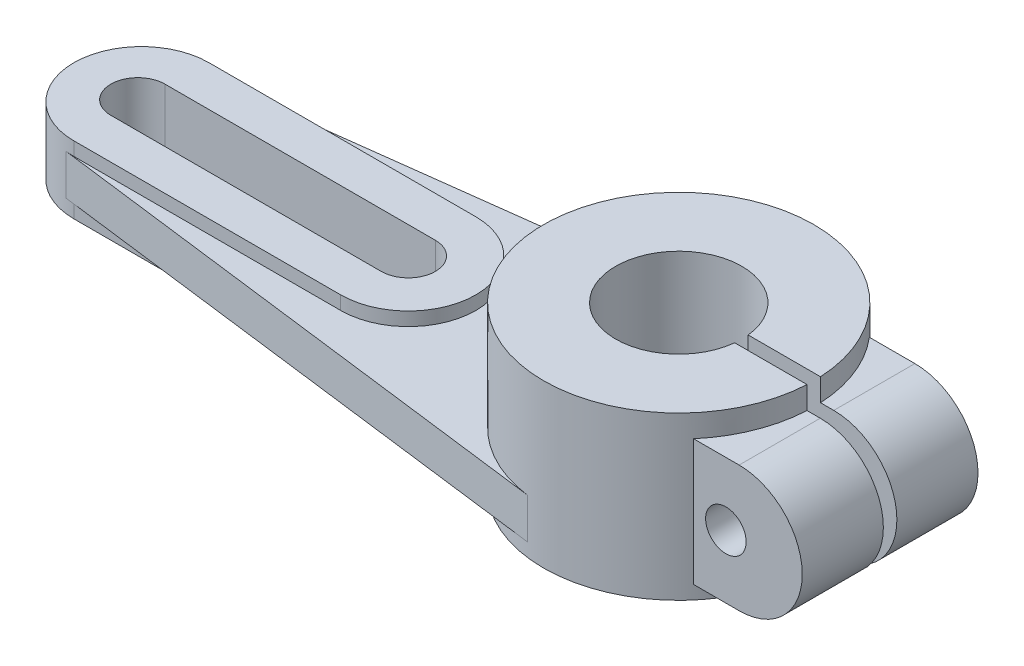
SolidWorks part; units mm, degrees
ref_plane "Front Plane" through (0, 0, 0) normal (0, 0, 1) x (1, 0, 0)
ref_plane "Top Plane" through (0, 0, 0) normal (0, 1, 0) x (1, 0, 0)
ref_plane "Right Plane" through (0, 0, 0) normal (1, 0, 0) x (0, 0, -1)
sketch "Sketch1" plane through (0, 0, 0) normal (0, 1, 0) x (1, 0, 0)
  line L0 (-60, 0) -> (-120, 0) construction
  line L1 (-60, -6) -> (-120, -6)
  line L2 (-60, 6) -> (-120, 6)
  line L3 (-119.2132, 0) -> (-60, 0) construction
  line L4 (-119.2132, 15) -> (-60, 15)
  line L5 (-119.2132, -15) -> (-60, -15)
  line L6 (13.9194, 1.5) -> (29.9625, 1.5)
  line L7 (13.9194, -1.5) -> (29.9625, -1.5)
  line L8 (0, 0) -> (13.9194, 1.5) construction
  line L9 (0, 0) -> (13.9194, -1.5) construction
  line L10 (-121.1005, 14.8808) -> (-3.7748, 29.7616)
  line L11 (-121.1005, -14.8808) -> (-3.7748, -29.7616)
  line L12 (22.798, -19.5) -> (46.9022, -19.5)
  line L13 (46.9022, -19.5) -> (46.9022, -1.5)
  line L14 (46.9022, -1.5) -> (29.9625, -1.5)
  line L15 (0, 0) -> (97.1806, 0) construction
  line L16 (29.9625, -1.5) -> (29.9625, -19.5)
  line L17 (46.9022, 19.5) -> (46.9022, 1.5)
  line L18 (22.798, 19.5) -> (46.9022, 19.5)
  line L19 (29.9625, 1.5) -> (29.9625, 19.5)
  line L20 (46.9022, 1.5) -> (29.9625, 1.5)
  arc A0 (13.9194, 1.5) -> (13.9194, -1.5) centre (0, 0) ccw
  arc A1 (29.9625, 1.5) -> (29.9625, -1.5) centre (0, 0) ccw
  arc A2 (-60, -6) -> (-60, 6) centre (-60, 0) ccw
  arc A3 (-120, 6) -> (-120, -6) centre (-120, 0) ccw
  arc A4 (-119.2132, 15) -> (-119.2132, -15) centre (-119.2132, 0) ccw
  arc A5 (-60, -15) -> (-60, 15) centre (-60, 0) ccw
  point P6 (-90, 0)
  point P13 (-89.6066, 0)
  dimension "D1" = 28
  dimension "D2" = 60
  dimension "D6" = 6
  dimension "D7" = 3
  dimension "D3" = 120
  dimension "D4" = 60
  dimension "D5" = 9
  dimension "D8" = 18
extrude "Boss-Extrude1" add sketch "Sketch1" along normal mid plane 15 contours L5 A5 L4 A4 A3 L2 A2 L1 region at (-89.6066, 0, -14.0588)
extrude "Boss-Extrude2" add sketch "Sketch1<3>" along normal mid plane 9 contours A5 L5 A4 L11 A1 L10 L4 region at (-62.2721, 0, -21.016)
sketch "Sketch1<3>" plane through (0, 0, 0) normal (0, 1, 0) x (1, 0, 0) same geometry as "Sketch1"
extrude "Boss-Extrude3" add sketch "Sketch1<4>" along normal blind 36 from surface contours A1 L7 A0 L6 region at (10.5017, 0, -27.1945) starting at face at (-90, -7.5, 0)
sketch "Sketch1<4>" plane through (0, 0, 0) normal (0, 1, 0) x (1, 0, 0) same geometry as "Sketch1"
extrude "Boss-Extrude4" add sketch "Sketch1<5>" along normal blind 28 from surface contours A1 L12 L16 | L14 L16 L12 L13 | L20 L17 L18 L19 | A1 L19 L18 region at (27.8593, 0, -14.8215) region at (38.4323, 0, -10.5) region at (27.8593, 0, 14.8215) region at (38.4323, 0, 10.5) starting at face at (-77.4257, -4.5, 0)
sketch "Sketch1<5>" plane through (0, 0, 0) normal (0, 1, 0) x (1, 0, 0) same geometry as "Sketch1"
fillet "Fillet1" 2 edges at (46.9022, 23.5, 10.5) (46.9022, -4.5, 10.5) type full round first side face at (37.0145, 23.5, 10.6486) second side face at (37.0145, -4.5, 10.6486) middle face at (46.9022, 9.5, 10.5)
fillet "Fillet2" 2 edges at (46.9022, 23.5, -10.5) (46.9022, -4.5, -10.5) type full round first side face at (37.0145, 23.5, -10.6486) second side face at (37.0145, -4.5, -10.6486) middle face at (46.9022, 9.5, -10.5)
sketch "Sketch2" plane through (0, 0, 19.5) normal (0, 0, 1) x (1, 0, 0)
  line L0 (29.9625, 23.5) -> (29.9625, -4.5) construction
  circle A0 centre (29.9625, 9.5) radius 4.5
  dimension "D1" = 9
extrude "Cut-Extrude1" cut sketch "Sketch2" against normal through all
